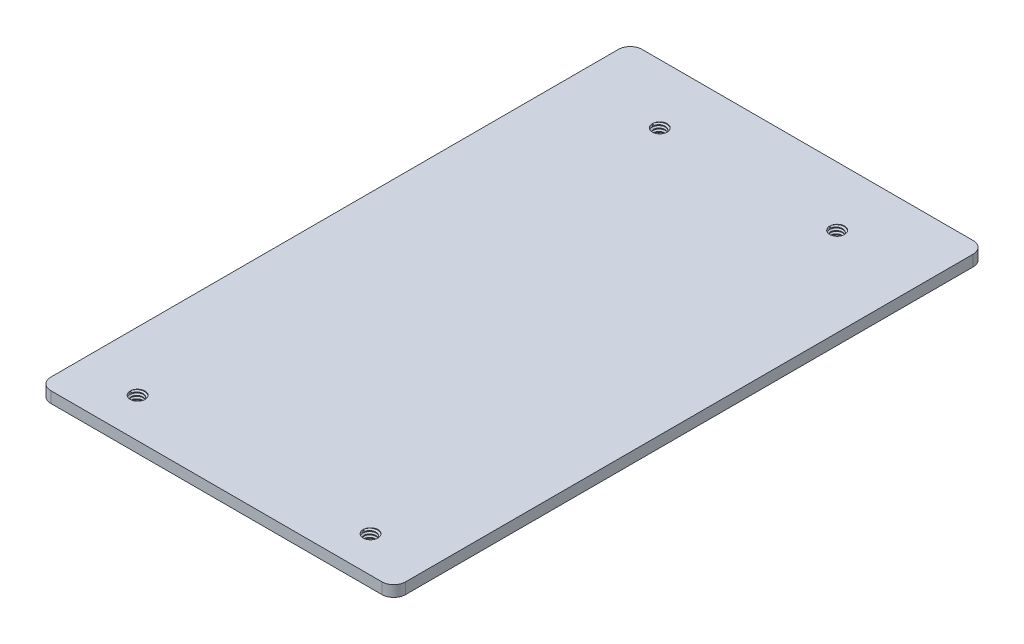
SolidWorks part; units mm, degrees
material "6061-T6 (SS)"
ref_plane "Front Plane" through (0, 0, 0) normal (0, 0, 1) x (1, 0, 0)
ref_plane "Top Plane" through (0, 0, 0) normal (0, 1, 0) x (1, 0, 0)
ref_plane "Right Plane" through (0, 0, 0) normal (1, 0, 0) x (0, 0, -1)
sketch "Sketch1" plane through (0, 0, 0) normal (0, 1, 0) x (1, 0, 0)
  line L1 (0, 0) -> (152.4, 0)
  line L2 (0, 0) -> (0, -254)
  line L3 (0, -254) -> (152.4, -254)
  line L4 (152.4, 0) -> (152.4, -254)
  dimension "D1" = 254
  dimension "D2" = 152.4
extrude "Boss-Extrude1" add sketch "Sketch1" along normal blind 4.7625
fillet "Fillet2" radius 5.08 1 edges at (152.4, 2.3813, 0)
fillet "Fillet3" radius 5.08 3 edges at (152.4, 2.3813, 254) (0, 2.3813, 254) (0, 2.3813, 0)
sketch "Sketch2" plane through (0, 4.7625, 0) normal (0, 1, 0) x (1, 0, 0)
  line L0 (76.2, -254) -> (76.2, 0) construction
  line L1 (5.08, -254) -> (147.32, -254) construction
  line L2 (147.32, 0) -> (5.08, 0) construction
sketch "Sketch9" plane through (0, 4.7625, 0) normal (0, 1, 0) x (1, 0, 0)
  line L0 (76.2, -254) -> (76.2, 0) construction
  line L1 (147.32, 0) -> (5.08, 0) construction
  circle A0 centre (114.3, -25.4) radius 3.175
  circle A1 centre (38.1, -25.4) radius 3.175
  circle A2 centre (127, -238.5666) radius 3.175
  circle A3 centre (25.4, -237.0458) radius 3.175
  dimension "D7" = 6.35
  dimension "D8" = 6.35
  dimension "D9" = 6.35
  dimension "D10" = 6.35
  dimension "D1" = 38.1
  dimension "D2" = 38.1
  dimension "D3" = 25.4
  dimension "D4" = 25.4
  dimension "D5" = 50.8
  dimension "D6" = 50.8
extrude "Cut-Extrude1" cut sketch "Sketch9" against normal through all
thread "Thread1" pitch 1.27 method extrude profile "Thread Profile2" start angle 0, offset 0, length 0, pitch 1.27, diameter 6.35
ref_plane "Plane16" through (22.225, 4.7625, 237.0458) normal (0, 0, 1) x (-1, 0, 0)
sketch "Thread Profile2" plane through (22.225, 4.7625, 237.0458) normal (0, 0, 1) x (-1, 0, 0)
  line L0 (0, 0) -> (0, 1.27) construction
  line L11 (0, 0) -> (0, 1.1112)
  line L12 (0, 1.1112) -> (-0.6874, 0.7144)
  line L13 (-0.6874, 0.7144) -> (-0.6874, 0.3969)
  line L15 (-0.6874, 0.3969) -> (0, 0)
  line L17 (-0.6874, 0.5556) -> (0, 0.5556) construction
  point P2 (0, 0)
  dimension "Pitch" = 1.27
  dimension "Profile_Angle" = 60
  dimension "Profile_Land" = 0.3175
  dimension "Profile_Height" = 0.6874
thread "Thread2" pitch 1.27 method extrude profile "Thread Profile3" start angle 0, offset 0, length 0, pitch 1.27, diameter 6.35
ref_plane "Plane17" through (34.925, 4.7625, 25.4) normal (0, 0, 1) x (-1, 0, 0)
sketch "Thread Profile3" plane through (34.925, 4.7625, 25.4) normal (0, 0, 1) x (-1, 0, 0)
  line L0 (0, 0) -> (0, 1.27) construction
  line L11 (0, 0) -> (0, 1.1112)
  line L12 (0, 1.1112) -> (-0.6874, 0.7144)
  line L13 (-0.6874, 0.7144) -> (-0.6874, 0.3969)
  line L15 (-0.6874, 0.3969) -> (0, 0)
  line L17 (-0.6874, 0.5556) -> (0, 0.5556) construction
  point P2 (0, 0)
  dimension "Pitch" = 1.27
  dimension "Profile_Angle" = 60
  dimension "Profile_Land" = 0.3175
  dimension "Profile_Height" = 0.6874
thread "Thread3" pitch 1.27 method extrude profile "Thread Profile4" start angle 0, offset 0, length 0, pitch 1.27, diameter 6.35
ref_plane "Plane18" through (111.125, 4.7625, 25.4) normal (0, 0, 1) x (-1, 0, 0)
sketch "Thread Profile4" plane through (111.125, 4.7625, 25.4) normal (0, 0, 1) x (-1, 0, 0)
  line L0 (0, 0) -> (0, 1.27) construction
  line L11 (0, 0) -> (0, 1.1112)
  line L12 (0, 1.1112) -> (-0.6874, 0.7144)
  line L13 (-0.6874, 0.7144) -> (-0.6874, 0.3969)
  line L15 (-0.6874, 0.3969) -> (0, 0)
  line L17 (-0.6874, 0.5556) -> (0, 0.5556) construction
  point P2 (0, 0)
  dimension "Pitch" = 1.27
  dimension "Profile_Angle" = 60
  dimension "Profile_Land" = 0.3175
  dimension "Profile_Height" = 0.6874
thread "Thread4" pitch 1.27 method extrude profile "Thread Profile5" start angle 0, offset 0, length 0, pitch 1.27, diameter 6.35
ref_plane "Plane19" through (123.825, 4.7625, 238.5666) normal (0, 0, 1) x (-1, 0, 0)
sketch "Thread Profile5" plane through (123.825, 4.7625, 238.5666) normal (0, 0, 1) x (-1, 0, 0)
  line L0 (0, 0) -> (0, 1.27) construction
  line L11 (0, 0) -> (0, 1.1112)
  line L12 (0, 1.1112) -> (-0.6874, 0.7144)
  line L13 (-0.6874, 0.7144) -> (-0.6874, 0.3969)
  line L15 (-0.6874, 0.3969) -> (0, 0)
  line L17 (-0.6874, 0.5556) -> (0, 0.5556) construction
  point P2 (0, 0)
  dimension "Pitch" = 1.27
  dimension "Profile_Angle" = 60
  dimension "Profile_Land" = 0.3175
  dimension "Profile_Height" = 0.6874
